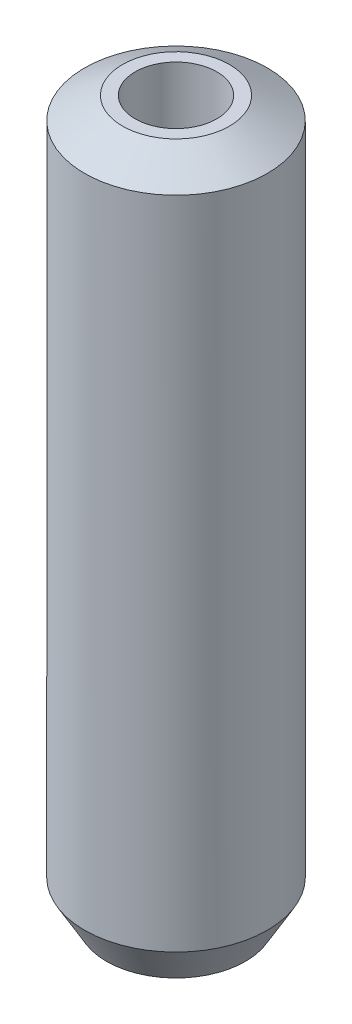
SolidWorks part; units mm, degrees
ref_plane "Front Plane" through (0, 0, 0) normal (0, 0, 1) x (1, 0, 0)
ref_plane "Top Plane" through (0, 0, 0) normal (0, 1, 0) x (1, 0, 0)
ref_plane "Right Plane" through (0, 0, 0) normal (1, 0, 0) x (0, 0, -1)
sketch "Sketch1" plane through (0, 0, 0) normal (0, 1, 0) x (1, 0, 0)
  circle A0 centre (0, 0) radius 15
  dimension "SHAFT_OD" = 30
extrude "Boss-Extrude1" add sketch "Sketch1" along normal blind 117.375
sketch "Sketch2" plane through (0, 0, 0) normal (0, 1, 0) x (1, 0, 0)
  circle A0 centre (0, 0) radius 6.6956
  dimension "BORE_D" = 13.3911
extrude "Cut-Extrude1" cut sketch "Sketch2" along normal through all
chamfer "Chamfer1" distance 3.5964 angle 60 2 edges at (0, 117.375, 15) (0, 0, 15) first distance on face at (0, 117.375, 15) first distance on face at (0, 0, 6.6956)
